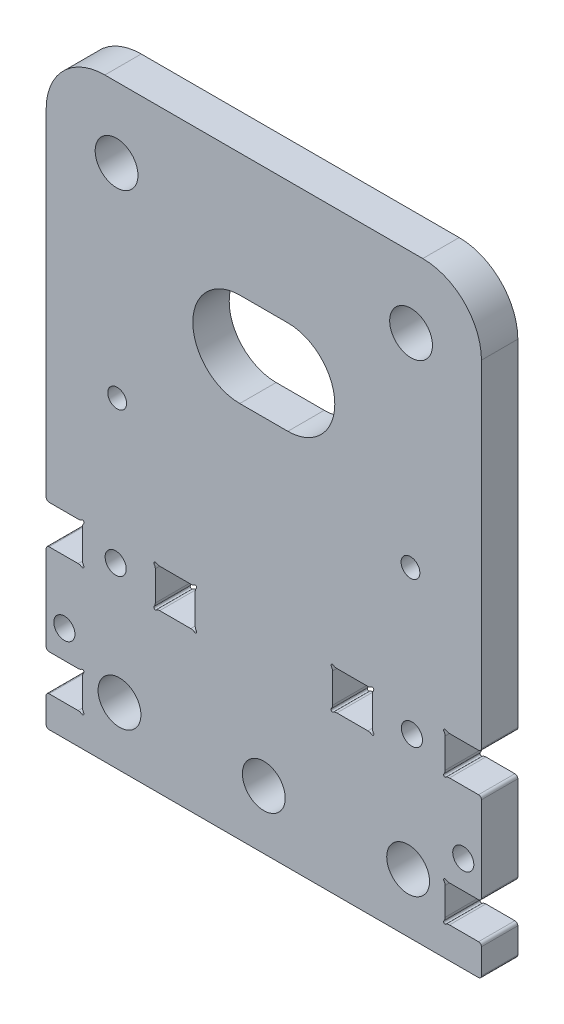
SolidWorks part; units mm, degrees
ref_plane "Front Plane" through (0, 0, 0) normal (0, 0, 1) x (1, 0, 0)
ref_plane "Top Plane" through (0, 0, 0) normal (0, 1, 0) x (1, 0, 0)
ref_plane "Right Plane" through (0, 0, 0) normal (1, 0, 0) x (0, 0, -1)
sketch "Sketch1" plane through (0, 0, 0) normal (0, 0, 1) x (1, 0, 0)
  line L0 (37.1, 0) -> (37.1, 59.3195) construction
  line L1 (0, 0) -> (74.2, 0)
  line L2 (0, 0) -> (0, 91.4)
  line L3 (10, 101.4) -> (64.2, 101.4)
  line L4 (74.2, 0) -> (74.2, 91.4)
  line L5 (0, 33.56) -> (74.2, 33.56) construction
  line L6 (-39.7056, 27) -> (34.4944, 27) construction
  line L7 (-40.5255, 5.3) -> (33.6745, 5.3) construction
  line L8 (-40.5255, 11.5) -> (33.6745, 11.5) construction
  line L9 (6.2, 79.4078) -> (6.2, -49920.5922) construction
  line L10 (68, 91.5017) -> (68, -49908.4983) construction
  line L11 (25.4, 75.1031) -> (25.4, -49924.8969) construction
  line L12 (18.6, 65.674) -> (18.6, -49934.326) construction
  line L13 (55.6, 36.7715) -> (55.6, -49963.2285) construction
  line L14 (48.8, 26.3174) -> (48.8, -49973.6826) construction
  line L16 (0, 33.56) -> (6.2, 33.56)
  line L17 (0, 33.56) -> (0, 27)
  line L18 (0, 27) -> (6.2, 27)
  line L19 (6.2, 33.56) -> (6.2, 27)
  line L20 (18.6, 33.56) -> (25.4, 33.56)
  line L21 (18.6, 33.56) -> (18.6, 27)
  line L22 (18.6, 27) -> (25.4, 27)
  line L23 (25.4, 33.56) -> (25.4, 27)
  line L24 (48.8, 33.56) -> (55.6, 33.56)
  line L25 (48.8, 33.56) -> (48.8, 27)
  line L26 (48.8, 27) -> (55.6, 27)
  line L27 (55.6, 33.56) -> (55.6, 27)
  line L28 (68, 33.56) -> (74.2, 33.56)
  line L29 (68, 33.56) -> (68, 27)
  line L30 (68, 27) -> (74.2, 27)
  line L31 (74.2, 33.56) -> (74.2, 27)
  line L32 (74.2, 5.3) -> (68, 5.3)
  line L33 (74.2, 5.3) -> (74.2, 11.5)
  line L34 (74.2, 11.5) -> (68, 11.5)
  line L35 (68, 5.3) -> (68, 11.5)
  line L36 (6.2, 11.5) -> (0, 11.5)
  line L37 (6.2, 11.5) -> (6.2, 5.3)
  line L38 (6.2, 5.3) -> (0, 5.3)
  line L39 (0, 11.5) -> (0, 5.3)
  arc A0 (64.2, 101.4) -> (74.2, 91.4) centre (64.2, 91.4) cw
  arc A1 (0, 91.4) -> (10, 101.4) centre (10, 91.4) cw
  circle A2 centre (12, 89.4) radius 3.65
  circle A3 centre (62.2, 89.4) radius 3.65
  circle A4 centre (37.1, 10) radius 3.65
  circle A5 centre (12.5, 10) radius 3.65
  circle A6 centre (61.7, 10) radius 3.65
  circle A7 centre (12.1, 54.75) radius 1.6
  circle A8 centre (62.1, 54.75) radius 1.6
  circle A9 centre (11.85, 30.28) radius 1.8
  circle A10 centre (3.1, 16.28) radius 1.8
  circle A11 centre (71.1, 16.28) radius 1.8
  circle A12 centre (62.35, 30.28) radius 1.8
  point P9 (0, 101.4)
  point P16 (37.1, 0)
  point P75 (6.2, 30.28)
  point P76 (3.1, 11.5)
  dimension "D3" = 10
  dimension "D8" = 7.3
  dimension "D9" = 7.3
  dimension "D11" = 6.2
  dimension "D12" = 6.2
  dimension "D14" = 3.2
  dimension "D27" = 3.6
  dimension "D28" = 7.3
  dimension "D1" = 74.2
  dimension "D2" = 101.4
  dimension "D4" = 12
  dimension "D5" = 12
  dimension "D6" = 12
  dimension "D7" = 12
  dimension "D10" = 10
  dimension "D13" = 49.2
  dimension "D15" = 50
  dimension "D16" = 54.75
  dimension "D17" = 6.8
  dimension "D18" = 6.8
  dimension "D19" = 12.4
  dimension "D20" = 12.4
  dimension "D21" = 5.3
  dimension "D22" = 6.2
  dimension "D23" = 15.5
  dimension "D24" = 6.56
  dimension "D25" = 16.28
  dimension "D26" = 50.5
extrude "Boss-Extrude1" add sketch "Sketch1" along normal blind 6.2 contours A1 L2 L16 L19 L18 L36 L37 L38 L1 L4 L32 L35 L34 L30 L29 L28 A0 L3 A11 A10 A9 A6 A5 A4 A3 A2 L20 L23 L22 L21 L24 L27 L26 L25 A7 region at (37.1, 51.7875, 0)
sketch "Sketch2" plane through (0, 0, 6.2) normal (0, 0, 1) x (1, 0, 0)
  line L0 (33, 72.4) -> (41.2, 72.4) construction
  line L1 (33, 80.4) -> (41.2, 80.4)
  line L2 (33, 64.4) -> (41.2, 64.4)
  line L3 (74.2, 33.56) -> (74.2, 91.4) construction
  line L4 (0, 33.56) -> (0, 91.4) construction
  line L5 (10, 101.4) -> (64.2, 101.4) construction
  arc A0 (33, 80.4) -> (33, 64.4) centre (33, 72.4) ccw
  arc A1 (41.2, 64.4) -> (41.2, 80.4) centre (41.2, 72.4) ccw
  point P2 (37.1, 72.4)
  dimension "D1" = 8
  dimension "D2" = 33
  dimension "D3" = 33
  dimension "D4" = 29
extrude "Cut-Extrude1" cut sketch "Sketch2" against normal through all
sketch "Sketch3" plane through (0, 0, 6.2) normal (0, 0, 1) x (1, 0, 0)
  circle A0 centre (6.2, 33.56) radius 0.25
  circle A1 centre (6.2, 27) radius 0.25
  circle A2 centre (6.2, 11.5) radius 0.25
  circle A3 centre (6.2, 5.3) radius 0.25
  circle A4 centre (25.4, 27) radius 0.25
  circle A5 centre (18.6, 27) radius 0.25
  circle A6 centre (18.6, 33.56) radius 0.25
  circle A7 centre (25.4, 33.56) radius 0.25
  circle A8 centre (48.8, 33.56) radius 0.25
  circle A9 centre (48.8, 27) radius 0.25
  circle A10 centre (55.6, 33.56) radius 0.25
  circle A11 centre (55.6, 27) radius 0.25
  circle A12 centre (68, 33.56) radius 0.25
  circle A13 centre (68, 27) radius 0.25
  circle A14 centre (68, 11.5) radius 0.25
  circle A15 centre (68, 5.3) radius 0.25
  dimension "D1" = 0.5
extrude "Cut-Extrude2" cut sketch "Sketch3" against normal through all
fillet "Fillet1" radius 1 32 edges at (5.95, 11.5, 3.1) (6.2, 11.25, 3.1) (6.2, 5.55, 3.1) (5.95, 5.3, 3.1) (68, 5.55, 3.1) (68.25, 5.3, 3.1) (68, 11.25, 3.1) (68.25, 11.5, 3.1) (68.25, 33.56, 3.1) (68, 33.31, 3.1) (68, 27.25, 3.1) (68.25, 27, 3.1) (48.8, 27.25, 3.1) (48.8, 33.31, 3.1) (49.05, 33.56, 3.1) (55.35, 33.56, 3.1) (55.6, 33.31, 3.1) (55.6, 27.25, 3.1) (55.35, 27, 3.1) (49.05, 27, 3.1) (18.6, 27.25, 3.1) (18.85, 27, 3.1) (25.15, 27, 3.1) (25.4, 27.25, 3.1) (25.4, 33.31, 3.1) (25.15, 33.56, 3.1) (18.85, 33.56, 3.1) (18.6, 33.31, 3.1) (5.95, 33.56, 3.1) (6.2, 33.31, 3.1) (6.2, 27.25, 3.1) (5.95, 27, 3.1)
fillet "Fillet2" radius 0.5 10 edges at (0, 0, 3.1) (74.2, 0, 3.1) (74.2, 33.56, 3.1) (74.2, 27, 3.1) (74.2, 5.3, 3.1) (74.2, 11.5, 3.1) (0, 5.3, 3.1) (0, 11.5, 3.1) (0, 33.56, 3.1) (0, 27, 3.1)
